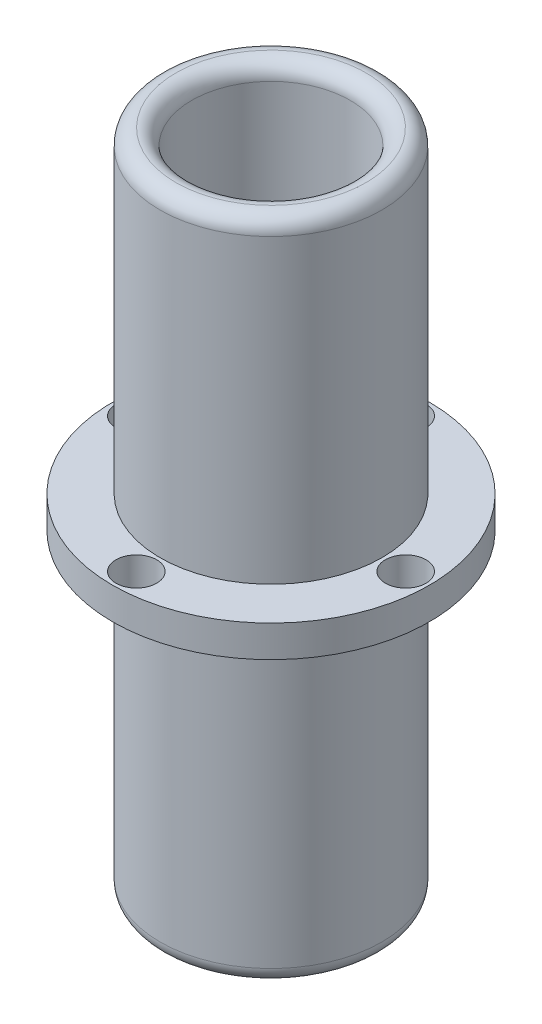
SolidWorks part; units mm, degrees
ref_plane "Front Plane" through (0, 0, 0) normal (0, 0, 1) x (1, 0, 0)
ref_plane "Top Plane" through (0, 0, 0) normal (0, 1, 0) x (1, 0, 0)
ref_plane "Right Plane" through (0, 0, 0) normal (1, 0, 0) x (0, 0, -1)
sketch "Sketch1" plane through (0, 0, 0) normal (0, 1, 0) x (1, 0, 0)
  circle A0 centre (0, 0) radius 6.35
  dimension "D1" = 12.7
extrude "Extrude-Thin1" add sketch "Sketch1" along normal blind 25.4 thin thin type one direction wall 2.54
sketch "Sketch2" plane through (0, 25.4, 0) normal (0, 1, 0) x (1, 0, 0)
  circle A0 centre (0, 0) radius 6.35
  circle A1 centre (0, 0) radius 12.7
  circle A3 centre (0, 0) radius 6.35 construction
  dimension "D1" = 25.4
extrude "Boss-Extrude1" add sketch "Sketch2" along normal blind 2.54
sketch "Sketch3" plane through (0, 27.94, 0) normal (0, 1, 0) x (1, 0, 0)
  circle A0 centre (0, 0) radius 6.35
  circle A4 centre (0, 0) radius 6.35 construction
extrude "Extrude-Thin2" add sketch "Sketch3" along normal blind 25.4 thin thin type one direction wall 2.54
sketch "Sketch4" plane through (0, 0, 0) normal (0, 0, 1) x (1, 0, 0)
  line L0 (0, 53.34) -> (0, 0) construction
  line L1 (6.35, 53.34) -> (-6.35, 53.34) construction
  line L2 (0, 26.67) -> (12.7, 26.67) construction
  circle A0 centre (0, 39.37) radius 4.1275
  dimension "D2" = 8.255
  dimension "D1" = 12.7
  dimension "D3" = 12.7
extrude "Cut-Extrude1" cut sketch "Sketch4" against normal blind 25.4
hole_wizard "#4 Clearance Hole1" positions "Sketch6" profile "Sketch5" hole size "#4" standard "Ansi Inch"
sketch "Sketch6" plane through (0, 27.94, 0) normal (0, 1, 0) x (-1, 0, 0)
  line L0 (-10.795, 0) -> (10.795, 0) construction
  line L2 (0, -10.795) -> (0, 10.795) construction
  circle A0 centre (0, 0) radius 10.795
  point P0 (-10.795, 0)
  point P1 (0, -10.795)
  point P3 (0, 10.795)
  point P5 (10.795, 0)
  dimension "D1" = 21.59
sketch "Sketch5" plane through (10.795, 27.94, 0) normal (1, 0, 0) x (0, 0, 1)
  line L0 (0, 0) -> (0, 26.3806)
  line L1 (0, 26.3806) -> (1.6319, 25.4)
  line L2 (1.6319, 25.4) -> (1.6319, 0)
  line L5 (1.6319, 0) -> (0, 0)
  line L10 (0, 26.3806) -> (-1.632, 25.4) construction
  line L11 (0, -6.35) -> (0, 107.95) construction
  dimension "Hole Dia." = 3.2639
  dimension "Hole Depth" = 25.4
  dimension "Drill Angle" = 118
fillet "Fillet2" radius 1.27 2 edges at (0, 0, 6.35) (8.89, 0, 0)
fillet "Fillet3" radius 1.27 2 edges at (0, 53.34, 6.35) (8.89, 53.34, 0)
